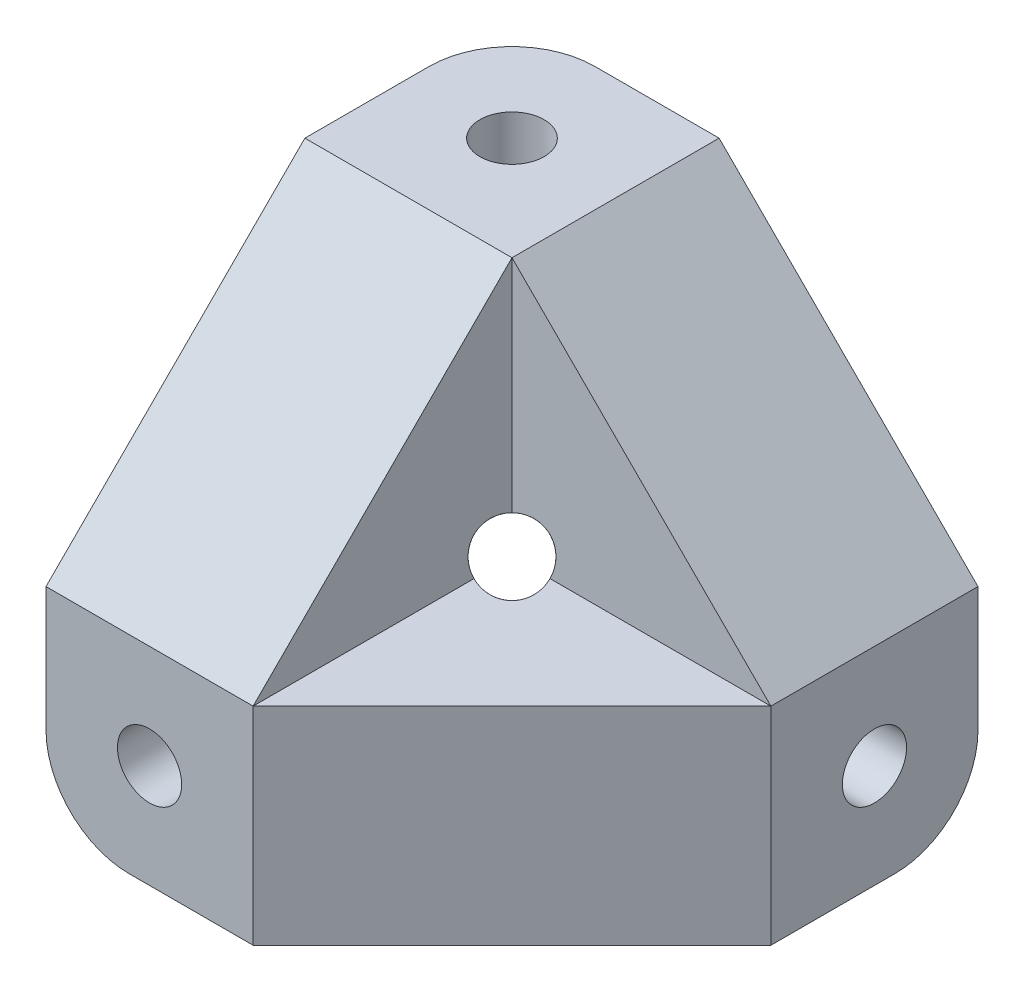
SolidWorks part; units mm, degrees
ref_plane "Front Plane" through (0, 0, 0) normal (0, 0, 1) x (1, 0, 0)
ref_plane "Top Plane" through (0, 0, 0) normal (0, 1, 0) x (1, 0, 0)
ref_plane "Right Plane" through (0, 0, 0) normal (1, 0, 0) x (0, 0, -1)
ref_plane "Plano1" through (0, 0, 20) normal (0, 0, 1) x (1, 0, 0)
sketch "Esboço1" plane through (0, 0, 20) normal (0, 0, 1) x (1, 0, 0)
  line L0 (9.638, 11.6423) -> (9.638, 56.6423)
  line L1 (9.638, 56.6423) -> (-35.362, 56.6423)
  line L2 (-35.362, 56.6423) -> (-35.362, 11.6423)
  line L3 (-35.362, 11.6423) -> (9.638, 11.6423)
extrude "Ressalto-extrusão1" add sketch "Esboço1" against normal blind 20
sketch "Esboço2" plane through (0, 0, 0) normal (0, 0, -1) x (-1, 0, 0)
  line L0 (15.362, 31.6423) -> (15.362, 56.6423)
  line L1 (15.362, 56.6423) -> (-9.638, 56.6423)
  line L2 (-9.638, 56.6423) -> (-9.638, 31.6423)
  line L3 (-9.638, 31.6423) -> (15.362, 31.6423)
extrude "Corte-extrusão1" cut sketch "Esboço2" against normal through all
sketch "Esboço3" plane through (0, 0, 20) normal (0, 0, 1) x (1, 0, 0)
  line L0 (-35.362, 31.6423) -> (-15.362, 31.6423)
  line L1 (-15.362, 31.6423) -> (-15.362, 11.6423)
  line L2 (-15.362, 11.6423) -> (-35.362, 11.6423)
  line L3 (-35.362, 11.6423) -> (-35.362, 31.6423)
extrude "Ressalto-extrusão2" add sketch "Esboço3" along normal blind 25
hole_wizard "Furo de diâmetro Ø6.2 (6.2)1" positions "Esboço5" profile "Esboço4" hole size "Ø6.2" standard "Ansi Metric"
sketch "Esboço5" plane through (9.638, 0, 0) normal (1, 0, 0) x (0, 0, -1)
  point P0 (-10, 21.6423)
sketch "Esboço4" plane through (9.638, 21.6423, 10) normal (0, 1, 0) x (0, 0, -1)
  line L0 (0, 0) -> (0, 35)
  line L1 (0, 35) -> (3.1, 35)
  line L2 (3.1, 35) -> (3.1, 0)
  line L5 (3.1, 0) -> (0, 0)
  line L10 (0, 35) -> (-3.1, 35) construction
  line L11 (0, -6.35) -> (0, 107.95) construction
  dimension "Hole Dia." = 6.2
  dimension "Hole Depth" = 35
  dimension "Drill Angle" = 180
hole_wizard "Furo de diâmetro Ø6.2 (6.2)2" positions "Esboço7" profile "Esboço6" hole size "Ø6.2" standard "Ansi Metric"
sketch "Esboço7" plane through (0, 56.6423, 0) normal (0, 1, 0) x (1, 0, 0)
  point P0 (-25.362, -10)
sketch "Esboço6" plane through (-25.362, 56.6423, 10) normal (1, 0, 0) x (0, 0, 1)
  line L0 (0, 0) -> (0, 35)
  line L1 (0, 35) -> (3.1, 35)
  line L2 (3.1, 35) -> (3.1, 0)
  line L5 (3.1, 0) -> (0, 0)
  line L10 (0, 35) -> (-3.1, 35) construction
  line L11 (0, -6.35) -> (0, 107.95) construction
  dimension "Hole Dia." = 6.2
  dimension "Hole Depth" = 35
  dimension "Drill Angle" = 180
hole_wizard "Furo de diâmetro Ø6.2 (6.2)3" positions "Esboço9" profile "Esboço8" hole size "Ø6.2" standard "Ansi Metric"
sketch "Esboço9" plane through (0, 0, 45) normal (0, 0, 1) x (1, 0, 0)
  point P0 (-25.362, 21.6423)
sketch "Esboço8" plane through (-25.362, 21.6423, 45) normal (1, 0, 0) x (0, -1, 0)
  line L0 (0, 0) -> (0, 35)
  line L1 (0, 35) -> (3.1, 35)
  line L2 (3.1, 35) -> (3.1, 0)
  line L5 (3.1, 0) -> (0, 0)
  line L10 (0, 35) -> (-3.1, 35) construction
  line L11 (0, -6.35) -> (0, 107.95) construction
  dimension "Hole Dia." = 6.2
  dimension "Hole Depth" = 35
  dimension "Drill Angle" = 180
fillet "Filete1" [suppressed] radius 4
fillet "Filete2" radius 8 3 edges at (-12.862, 11.6423, 0) (-35.362, 34.1423, 0) (-35.362, 11.6423, 22.5)
chamfer "Chanfro1" distance 25 angle 45 1 edges at (-25.362, 31.6423, 20)
chamfer "Chanfro2" distance 25 angle 45 1 edges at (-15.362, 31.6423, 10)
sketch "Esboço10" plane through (0, 11.6423, 0) normal (0, -1, 0) x (1, 0, 0)
  line L0 (-15.362, 45) -> (9.638, 20)
  line L1 (9.638, 20) -> (-15.362, 20)
  line L2 (-15.362, 20) -> (-15.362, 45)
extrude "Ressalto-extrusão3" add sketch "Esboço10" against normal blind 20
ref_plane "Plano2" through (20.4267, 20.4267, 20.4267) normal (-0.5774, -0.5774, -0.5774) x (-0.8165, 0.4082, 0.4082)
sketch "Esboço12" plane through (20.4267, 20.4267, 20.4267) normal (-0.5774, -0.5774, -0.5774) x (-0.8165, 0.4082, 0.4082)
  circle A0 centre (33.6259, 8.2323) radius 3
  dimension "D1" = 6
extrude "Corte-extrusão2" cut sketch "Esboço12" along normal through all
